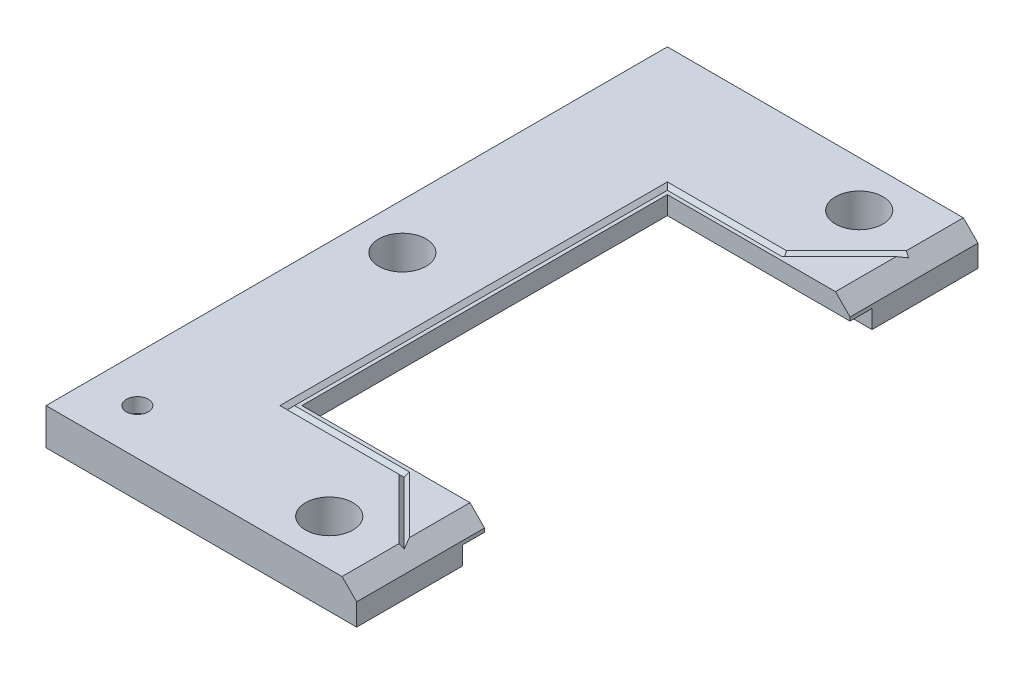
SolidWorks part; units mm, degrees
ref_plane "Front Plane" through (0, 0, 0) normal (0, 0, 1) x (1, 0, 0)
ref_plane "Top Plane" through (0, 0, 0) normal (0, 1, 0) x (1, 0, 0)
ref_plane "Right Plane" through (0, 0, 0) normal (1, 0, 0) x (0, 0, -1)
sketch "Sketch1" plane through (0, 0, 0) normal (0, 1, 0) x (1, 0, 0)
  line L0 (0, -85) -> (0, -50)
  line L1 (-85, -85) -> (0, -85)
  line L2 (-85, -85) -> (-85, 85)
  line L3 (-85, 85) -> (0, 85)
  line L5 (-85, -85) -> (-50, -50) construction
  line L6 (-85, 85) -> (-50, 50) construction
  line L7 (-50, -50) -> (0, -50)
  line L8 (-50, -50) -> (-50, 50)
  line L9 (-50, 50) -> (0, 50)
  line L13 (0, 50) -> (0, 85)
  point P1 (0, 0)
  point P6 (0, 0)
  point P14 (0, 0)
  dimension "D1" = 35
  dimension "D2" = 35
  dimension "D3" = 100
  dimension "D4" = 85
  dimension "D5" = 35
extrude "Boss-Extrude1" add sketch "Sketch1" along normal blind 10
sketch "Sketch3" plane through (0, 0, 0) normal (1, 0, 0) x (0, 0, -1)
  line L1 (-50, 0) -> (-56, 0)
  line L2 (-50, 0) -> (-50, 5)
  line L3 (-50, 5) -> (-56, 5)
  line L4 (-56, 0) -> (-56, 5)
  dimension "D1" = 5
  dimension "D2" = 6
sketch "Sketch4" plane through (0, 0, 0) normal (0, -1, 0) x (1, 0, 0)
  line L0 (0, 50) -> (-50, 50)
  line L1 (-50, 50) -> (-50, -50) construction
  line L2 (0, 50) -> (-50, 50) construction
  line L3 (-50, 50) -> (-50, -50)
  line L4 (-50, -50) -> (0, -50)
sweep "Cut-Sweep1" cut profiles "Sketch3" path "Sketch4"
chamfer "Chamfer1" distance 4 angle 45 2 edges at (0, 10, 67.5) (0, 10, -67.5)
sketch "Sketch7" plane through (0, 0, 0) normal (1, 0, 0) x (0, 0, -1)
  line L1 (-50, 6) -> (-85, 6) construction
  line L2 (-85, 0) -> (-56, 0) construction
  line L3 (-72, 6) -> (-72, 0)
  line L4 (-85, 6) -> (-85, 0) construction
  dimension "D1" = 13
ref_axis "Axis1" through (0, 6, 72) along (0, -1, 0)
ref_plane "Plane1" through (36, 0, 36) normal (0.7071, 0, 0.7071) x (0, -1, 0)
sketch "Sketch5" plane through (0, 10, 0) normal (0, 1, 0) x (1, 0, 0)
  line L0 (-20, -52) -> (-52, -52)
  line L1 (-20, -52) -> (0, -72)
  line L2 (-52, -52) -> (-52, 52)
  line L3 (-20, 52) -> (0, 72)
  line L4 (0, -50) -> (0, -85) construction
  line L6 (-50, -50) -> (-50, 50) construction
  line L7 (-4, -50) -> (-50, -50) construction
  line L8 (0, 0) -> (-96.1045, 0) construction
  line L9 (-20, 52) -> (-52, 52)
  point P2 (-52, 0)
  dimension "D2" = 2
  dimension "D3" = 2
  dimension "D4" = 13
  dimension "D5" = 45
sketch "Sketch9" plane through (36, 0, 36) normal (0.7071, 0, 0.7071) x (0, -1, 0)
  line L2 (-6, -50.9117) -> (-10, -50.9117) construction
  line L7 (-10, 0) -> (-10, -67.9561) construction
  line L8 (-6, -50.9117) -> (0, -50.9117) construction
  line L9 (-10, -50.9117) -> (-10, -51.9117)
  line L10 (-10, -51.9117) -> (-9, -50.9117)
  line L11 (-9, -50.9117) -> (-10, -49.9117)
  line L12 (-10, -49.9117) -> (-10, -50.9117)
  dimension "D1" = 1
  dimension "D2" = 45
sketch "Sketch10" plane through (0, 10, 0) normal (0, 1, 0) x (1, 0, 0)
  circle A0 centre (-72.5, 0) radius 6.5
  circle A1 centre (-20, -72.5) radius 6.5
  circle A3 centre (-20, 72.5) radius 6.5
extrude "Cut-Extrude1" cut sketch "Sketch10" against normal through all
sketch "Sketch11" plane through (0, 10, 0) normal (0, 1, 0) x (1, 0, 0)
  circle A0 centre (-72.5, -72.5) radius 3
hole_wizard "Ø6.0mm Dowel Hole1" positions "Sketch12" profile "Sketch13" hole size "Ø6.0" standard "ISO"
sketch "Sketch12" plane through (0, 10, 0) normal (0, 1, 0) x (1, 0, 0)
  point P0 (-72.5, -72.5)
sketch "Sketch13" plane through (-72.5, 10, 72.5) normal (1, 0, 0) x (0, 0, 1)
  line L0 (0, 0) -> (0, 5.8026)
  line L1 (0, 5.8026) -> (3, 4)
  line L2 (3, 4) -> (3, 0)
  line L5 (3, 0) -> (0, 0)
  line L10 (0, 5.8026) -> (-3, 4) construction
  line L11 (0, -6.35) -> (0, 107.95) construction
  dimension "Hole Dia." = 6
  dimension "Hole Depth" = 4
  dimension "Drill Angle" = 118
sweep "Cut-Sweep2" cut profiles "Sketch9" path "Sketch5"
